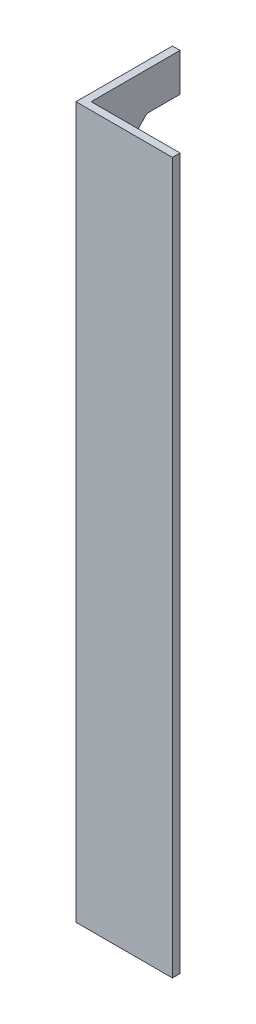
SolidWorks part; units mm, degrees
ref_plane "Alzado" through (0, 0, 0) normal (0, 0, 1) x (1, 0, 0)
ref_plane "Planta" through (0, 0, 0) normal (0, 1, 0) x (1, 0, 0)
ref_plane "Vista lateral" through (0, 0, 0) normal (1, 0, 0) x (0, 0, -1)
sketch "Croquis1" plane through (0, 0, 0) normal (0, 1, 0) x (1, 0, 0)
  line L0 (0, 0) -> (0, 38)
  line L1 (0, 0) -> (38, 0)
  line L2 (3, 3) -> (38, 3)
  line L3 (3, 3) -> (3, 38)
  line L4 (0, 38) -> (3, 38)
  line L5 (38, 3) -> (38, 0)
  dimension "D1" = 38
  dimension "D2" = 3
extrude "Saliente-Extruir1" add sketch "Croquis1" along normal blind 280
sketch "Croquis2" plane through (0, 0, 0) normal (-1, 0, 0) x (0, 0, 1)
  line L0 (-15, 0) -> (-15, 280) construction
  line L1 (-38, 0) -> (0, 0) construction
  line L2 (-38, 280) -> (0, 280) construction
  line L3 (-38, 280) -> (-38, 0) construction
  line L4 (0, 280) -> (0, 0) construction
  line L5 (-38, 15) -> (-15, 15)
  line L6 (-38, 280) -> (-38, 0) construction
  line L7 (-15, 15) -> (-15, 265)
  line L8 (-15, 265) -> (-38, 265)
  line L9 (-38, 15) -> (-38, 265)
  dimension "D1" = 15
  dimension "D2" = 15
  dimension "D3" = 15
extrude "Cortar-Extruir1" cut sketch "Croquis2" against normal up to surface (3 mm away) up to face at (3, 140, -20.5)
chamfer "Chaflán1" distance 10 angle 45 2 edges at (1.5, 15, -15) (1.5, 265, -15)
sketch "Croquis3" plane through (0, 0, 0) normal (0, 0, 1) x (1, 0, 0)
  circle A0 centre (21, 179.5) radius 5 construction
  circle A1 centre (21, 179.5) radius 5
